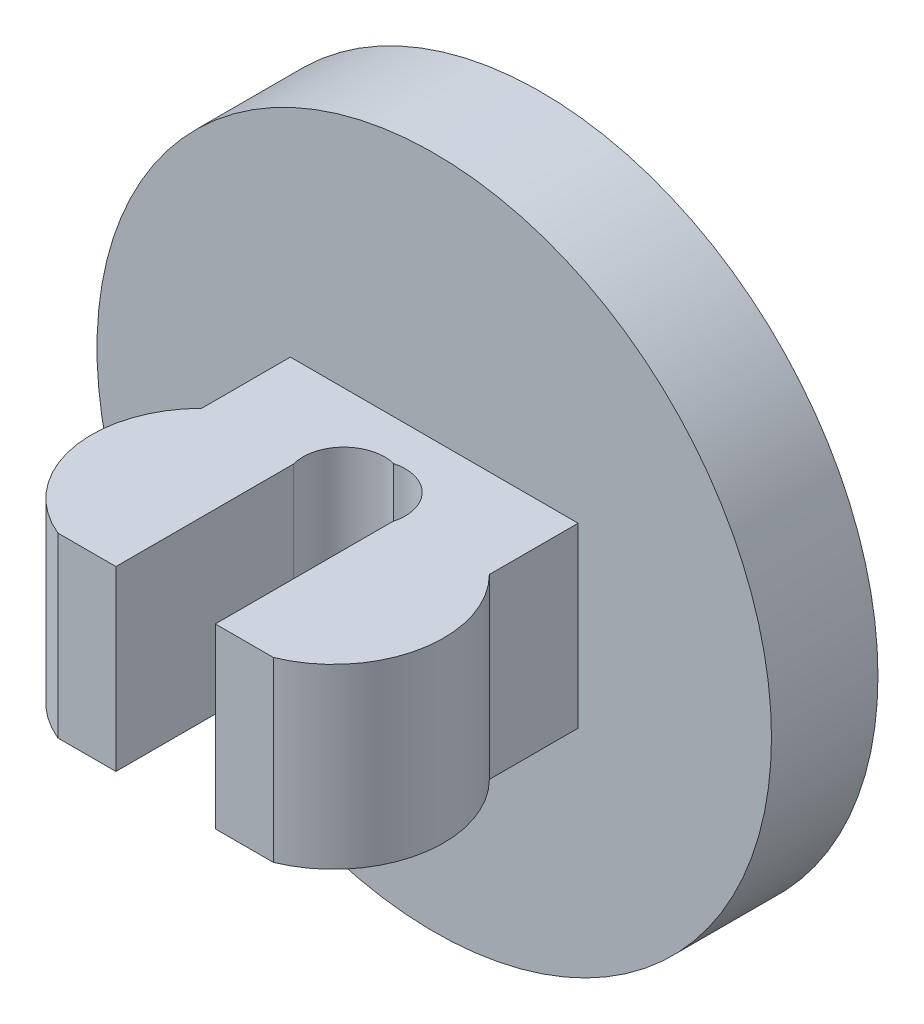
SolidWorks part; units mm, degrees
ref_plane "Front Plane" through (0, 0, 0) normal (0, 0, 1) x (1, 0, 0)
ref_plane "Top Plane" through (0, 0, 0) normal (0, 1, 0) x (1, 0, 0)
ref_plane "Right Plane" through (0, 0, 0) normal (1, 0, 0) x (0, 0, -1)
sketch "Sketch1" plane through (0, 0, 0) normal (0, 0, 1) x (1, 0, 0)
  circle A0 centre (0, 0) radius 9.5
  dimension "D1" = 19
extrude "Boss-Extrude1" add sketch "Sketch1" along normal blind 3
sketch "Sketch3" plane through (0, 0, 0) normal (0, 1, 0) x (1, 0, 0)
  line L0 (-9.5, -3) -> (9.5, -3) construction
  line L1 (0, 0) -> (0, -14.3724) construction
  line L8 (-4.053, -5.5) -> (-4.053, -3)
  line L11 (-3.0361, -10.5668) -> (-1.4, -10.5668)
  line L12 (-1.4, -10.5668) -> (-1.4, -5.5668)
  line L13 (-4.053, -3) -> (4.053, -3)
  line L14 (1.4, -10.5668) -> (1.4, -5.5668)
  line L15 (3.0361, -10.5668) -> (1.4, -10.5668)
  line L16 (4.053, -5.5) -> (4.053, -3)
  arc A8 (-1.4, -5.5668) -> (0, -4.1424) centre (-0.289, -5.2586) cw
  arc A10 (-3.0361, -10.5668) -> (-4.053, -5.5) centre (-1.8537, -7.6941) cw
  arc A11 (3.0361, -10.5668) -> (4.053, -5.5) centre (1.8537, -7.6941) ccw
  arc A12 (1.4, -5.5668) -> (0, -4.1424) centre (0.289, -5.2586) ccw
  point P21 (0, -3)
  point P25 (0, -3)
  dimension "D5" = 3.1066
  dimension "D8" = 1.153
  dimension "D1" = 2.653
  dimension "D2" = 1.4
  dimension "D3" = 1.6361
  dimension "D4" = 5.0668
  dimension "D6" = 5
  dimension "D7" = 1.4244
  dimension "D9" = 2.5
extrude "Boss-Extrude2" add sketch "Sketch3" along normal mid plane 5
sketch "Sketch4" plane through (0, 0, 0) normal (0, 1, 0) x (1, 0, 0)
  line L0 (-4.9603, -7.6941) -> (0, -7.6941) construction
  line L1 (-1.4, -10.5668) -> (-1.4, -5.5668) construction
  line L3 (-4.053, -3) -> (0, -3) construction
  line L4 (4.053, -3) -> (-4.053, -3) construction
  line L5 (-3.0361, -10.5668) -> (-1.4, -10.5668) construction
  arc A0 (-4.053, -5.5) -> (-3.0361, -10.5668) centre (-1.8537, -7.6941) ccw construction
  dimension "D1" = 4.9603
  dimension "D2" = 7.5668
  dimension "D3" = 1.4
sketch "Sketch5" plane through (0, 0, 3) normal (0, 0, 1) x (1, 0, 0)
  line L0 (0, 0) -> (0, 5.395)
sketch "Sketch6" plane through (0, 0, 0) normal (0, 0, 1) x (1, 0, 0)
  line L0 (0, 0) -> (0, 5.395)
